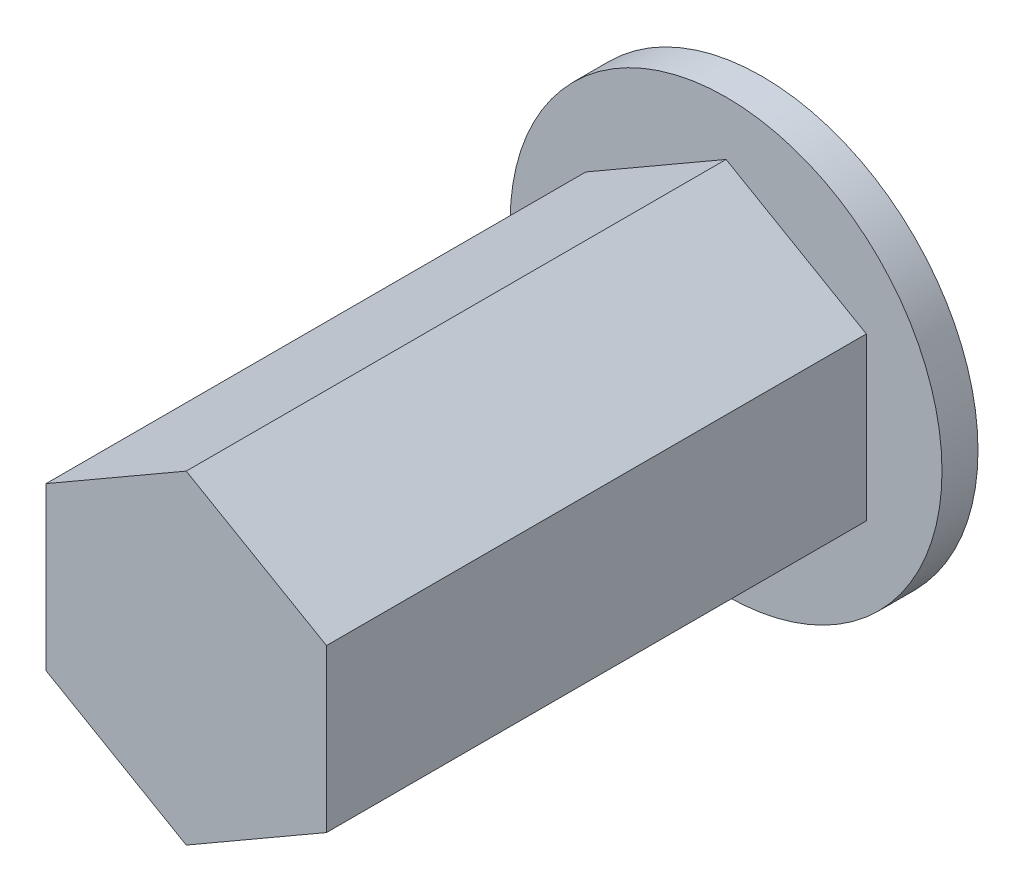
SolidWorks part; units mm, degrees
ref_plane "Alzado" through (0, 0, 0) normal (0, 0, 1) x (1, 0, 0)
ref_plane "Planta" through (0, 0, 0) normal (0, 1, 0) x (1, 0, 0)
ref_plane "Vista lateral" through (0, 0, 0) normal (1, 0, 0) x (0, 0, -1)
sketch "Croquis1" plane through (0, 0, 0) normal (0, 0, 1) x (1, 0, 0)
  line L1 (0, 9) -> (-7.7942, 4.5)
  line L2 (-7.7942, 4.5) -> (-7.7942, -4.5)
  line L3 (-7.7942, -4.5) -> (0, -9)
  line L4 (0, -9) -> (7.7942, -4.5)
  line L5 (7.7942, -4.5) -> (7.7942, 4.5)
  line L6 (7.7942, 4.5) -> (0, 9)
  circle A0 centre (0, 0) radius 7.7942 construction
  dimension "D1" = 9
extrude "Saliente-Extruir1" add sketch "Croquis1" along normal blind 30
sketch "Croquis2" plane through (0, 0, 0) normal (0, 0, -1) x (-1, 0, 0)
  circle A0 centre (0, 0) radius 12
  dimension "D1" = 24
extrude "Saliente-Extruir2" add sketch "Croquis2" along normal blind 2
